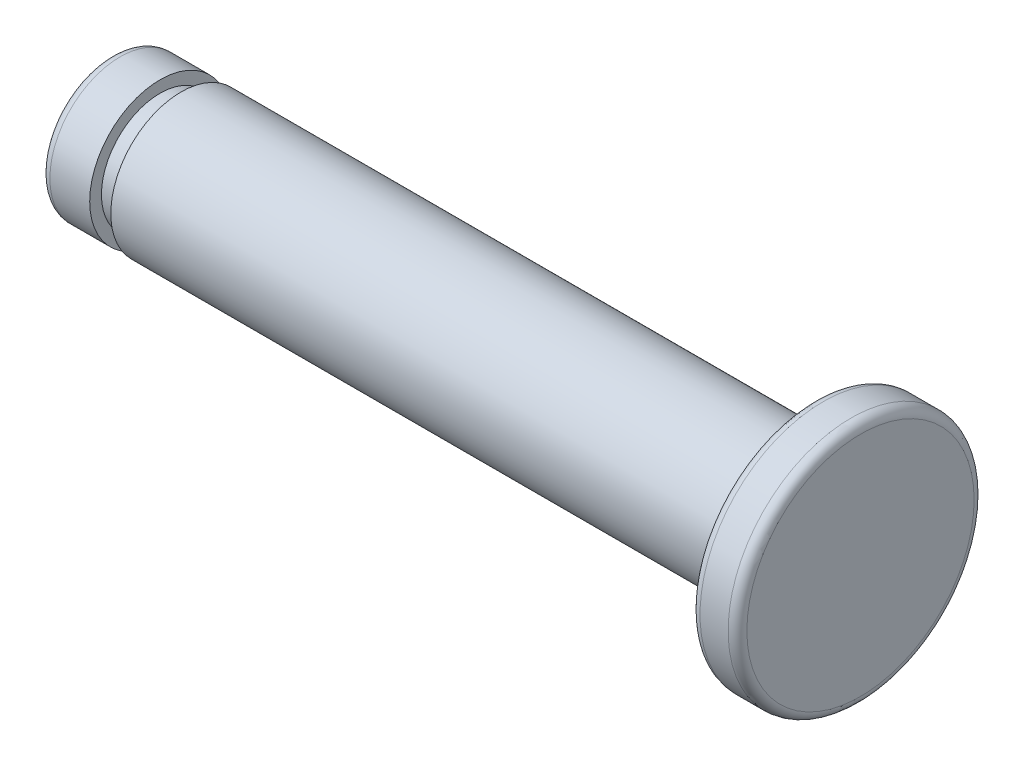
SolidWorks part; units mm, degrees
ref_plane "前视基准面" through (0, 0, 0) normal (0, 0, 1) x (1, 0, 0)
ref_plane "上视基准面" through (0, 0, 0) normal (0, 1, 0) x (1, 0, 0)
ref_plane "右视基准面" through (0, 0, 0) normal (1, 0, 0) x (0, 0, -1)
sketch "草图1" plane through (0, 0, 0) normal (1, 0, 0) x (0, 0, -1)
  circle A0 centre (0, 0) radius 5.25
  circle A1 centre (0, 0) radius 3
extrude "凸台-拉伸1" add sketch "草图1" along normal blind 2 contours A1 | A0 A1 region at (0, 0, 5.1015) region at (0, 0, 0)
extrude "凸台-拉伸2" add sketch "草图1<4>" against normal blind 27 contours A1 region at (0, 0, 0)
sketch "草图1<4>" plane through (0, 0, 0) normal (1, 0, 0) x (0, 0, -1) same geometry as "草图1"
fillet "圆角1" radius 0.4 2 edges at (2, 0, -5.25) (0, 0, -5.25)
sketch "草图2" plane through (-27, 0, 0) normal (-1, 0, 0) x (0, 0, 1)
  circle A0 centre (0, 0) radius 2.5
extrude "凸台-拉伸3" add sketch "草图2" along normal blind 0.9
sketch "草图3" plane through (-27.9, 0, 0) normal (-1, 0, 0) x (0, 0, 1)
  circle A0 centre (0, 0) radius 3
extrude "凸台-拉伸4" add sketch "草图3" along normal blind 2.1
fillet "圆角2" radius 0.4 1 edges at (-30, 0, 3)
